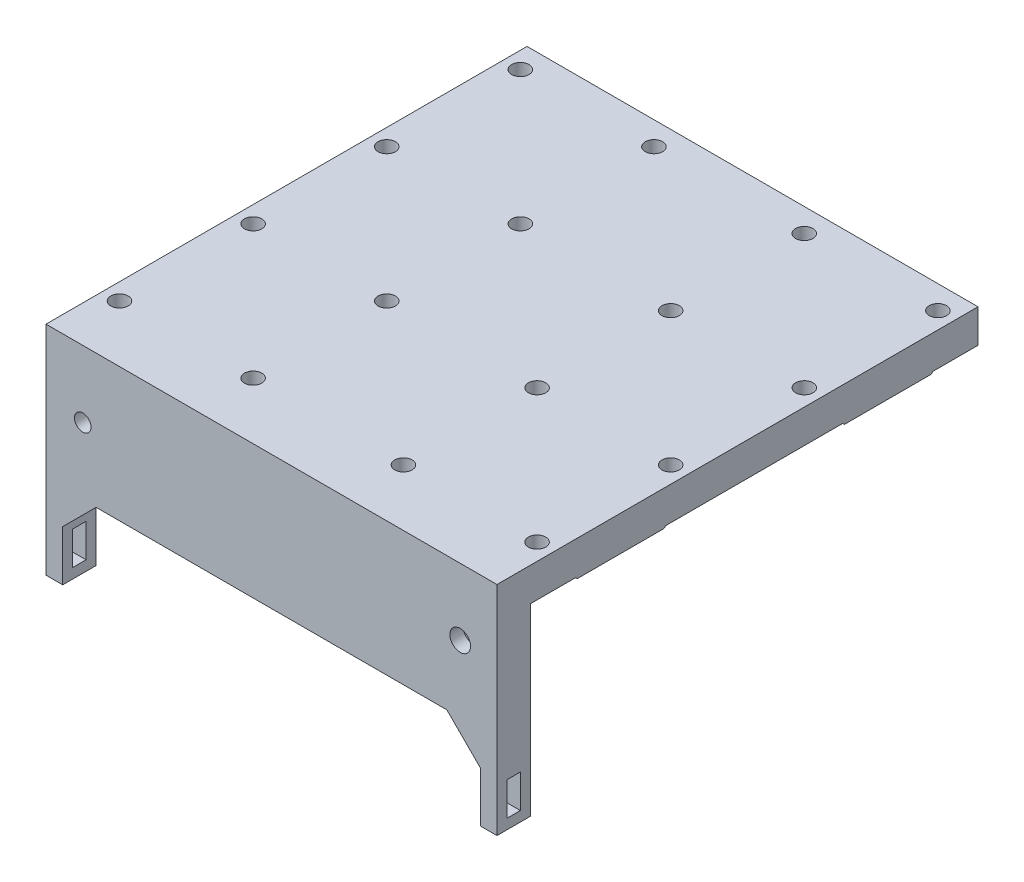
SolidWorks part; units mm, degrees
ref_plane "Płaszczyzna przednia" through (0, 0, 0) normal (0, 0, 1) x (1, 0, 0)
ref_plane "Płaszczyzna górna" through (0, 0, 0) normal (0, 1, 0) x (1, 0, 0)
ref_plane "Płaszczyzna prawa" through (0, 0, 0) normal (1, 0, 0) x (0, 0, -1)
sketch "Sketch1" plane through (0, 0, 0) normal (0, 1, 0) x (1, 0, 0)
  line L6 (-67.5, -67) -> (67.5, -67)
  line L12 (-67.5, -67) -> (-67.5, 67)
  line L18 (-67.5, 67) -> (67.5, 67)
  line L20 (67.5, -67) -> (67.5, 67)
  line L25 (-67.5, -67) -> (67.5, 67) construction
  line L26 (-67.5, 67) -> (67.5, -67) construction
  point P0 (0, 0)
  dimension "D1" = 134
  dimension "D2" = 135
extrude "Boss-Extrude1" add sketch "Sketch1" along normal blind 10
sketch "Sketch2" plane through (0, 0, 0) normal (0, 1, 0) x (1, 0, 0)
  line L0 (-67.5, 67) -> (-67.5, -67) construction
  line L1 (-67.5, 26.5) -> (-17.5, 26.5)
  line L2 (-67.5, 26.5) -> (-67.5, 53.5)
  line L3 (-67.5, 53.5) -> (-17.5, 53.5)
  line L4 (-17.5, 26.5) -> (-17.5, 53.5)
  line L5 (67.5, 67) -> (-67.5, 67) construction
  line L6 (-22, 0) -> (22, 0) construction
  line L7 (-17.5, -26.5) -> (-17.5, -53.5)
  line L8 (-67.5, -53.5) -> (-17.5, -53.5)
  line L9 (-67.5, -26.5) -> (-67.5, -53.5)
  line L10 (-67.5, -26.5) -> (-17.5, -26.5)
  line L11 (0, -22) -> (0, 22) construction
  line L12 (67.5, -26.5) -> (17.5, -26.5)
  line L13 (67.5, -26.5) -> (67.5, -53.5)
  line L14 (67.5, -53.5) -> (17.5, -53.5)
  line L15 (17.5, -26.5) -> (17.5, -53.5)
  line L16 (17.5, 26.5) -> (17.5, 53.5)
  line L17 (67.5, 53.5) -> (17.5, 53.5)
  line L18 (67.5, 26.5) -> (67.5, 53.5)
  line L19 (67.5, 26.5) -> (17.5, 26.5)
  dimension "D1" = 50
  dimension "D2" = 27
  dimension "D3" = 13.5
extrude "Boss-Extrude2" add sketch "Sketch2" against normal blind 0.5
sketch "Sketch3" plane through (0, 0, 0) normal (0, 1, 0) x (1, 0, 0)
  line L0 (-67.5, 67) -> (-67.5, -67) construction
  line L1 (-62.5, 20) -> (-22.5, 20) construction
  line L2 (-62.5, 20) -> (-62.5, 60) construction
  line L3 (-62.5, 60) -> (-22.5, 60) construction
  line L4 (-22.5, 20) -> (-22.5, 60) construction
  line L5 (67.5, 67) -> (-67.5, 67) construction
  line L6 (-22, 0) -> (22, 0) construction
  line L7 (-22.5, -20) -> (-22.5, -60) construction
  line L8 (-62.5, -60) -> (-22.5, -60) construction
  line L9 (-62.5, -20) -> (-62.5, -60) construction
  line L10 (-62.5, -20) -> (-22.5, -20) construction
  line L11 (0, -22) -> (0, 22) construction
  line L12 (62.5, -20) -> (22.5, -20) construction
  line L13 (62.5, -20) -> (62.5, -60) construction
  line L14 (62.5, -60) -> (22.5, -60) construction
  line L15 (22.5, -20) -> (22.5, -60) construction
  line L16 (22.5, 20) -> (22.5, 60) construction
  line L17 (62.5, 60) -> (22.5, 60) construction
  line L18 (62.5, 20) -> (62.5, 60) construction
  line L19 (62.5, 20) -> (22.5, 20) construction
  circle A0 centre (-62.5, 20) radius 2.6
  circle A1 centre (-22.5, 20) radius 2.6
  circle A2 centre (-22.5, 60) radius 2.6
  circle A3 centre (-62.5, 60) radius 2.6
  circle A4 centre (-62.5, -60) radius 2.6
  circle A5 centre (-22.5, -60) radius 2.6
  circle A6 centre (-22.5, -20) radius 2.6
  circle A7 centre (-62.5, -20) radius 2.6
  circle A8 centre (62.5, -20) radius 2.6
  circle A9 centre (22.5, -20) radius 2.6
  circle A10 centre (22.5, -60) radius 2.6
  circle A11 centre (62.5, -60) radius 2.6
  circle A12 centre (62.5, 60) radius 2.6
  circle A13 centre (22.5, 60) radius 2.6
  circle A14 centre (22.5, 20) radius 2.6
  circle A15 centre (62.5, 20) radius 2.6
  dimension "D1" = 5.2
  dimension "D2" = 40
  dimension "D3" = 5
  dimension "D4" = 7
extrude "Cut-Extrude1" cut sketch "Sketch3" against normal through all both and the other way through all
sketch "Sketch4" plane through (0, 0, 0) normal (0, 0, 1) x (1, 0, 0)
  line L0 (67.5, 10) -> (67.5, 0) construction
  line L1 (-67.5, 10) -> (67.5, 10)
  line L2 (-67.5, 10) -> (-67.5, -30)
  line L3 (-67.5, -30) -> (67.5, -30)
  line L4 (67.5, 10) -> (67.5, -30)
  line L5 (-67.5, 0) -> (67.5, 0) construction
  dimension "D1" = 30
extrude "Boss-Extrude3" add sketch "Sketch4" along normal blind 10 from surface starting at face at (0, 5, 67)
sketch "Sketch5" plane through (0, 0, 0) normal (0, 0, 1) x (1, 0, 0)
  line L0 (-67.5, -10) -> (67.5, -10) construction
  line L1 (-67.5, 10) -> (-67.5, -30) construction
  line L2 (67.5, -30) -> (67.5, 10) construction
  circle A0 centre (-56.5, -10) radius 2.4889
  circle A1 centre (56.5, -10) radius 3.1003
  dimension "D1" = 56.5
  dimension "D2" = 56.5
extrude "Cut-Extrude2" cut sketch "Sketch5" against normal through all both and the other way through all from surface starting at face at (0, -10, 77)
chamfer "Chamfer1" distance 0.5 angle 45 8 edges at (42.5, -0.5, 26.5) (42.5, -0.5, 53.5) (-42.5, -0.5, 53.5) (-42.5, -0.5, 26.5) (-42.5, -0.5, -53.5) (-42.5, -0.5, -26.5) (42.5, -0.5, -26.5) (42.5, -0.5, -53.5)
sketch "Sketch6" plane through (0, 0, 0) normal (0, 0, 1) x (1, 0, 0)
  circle A0 centre (56.5, -10) radius 5.25
  circle A1 centre (-56.5, -10) radius 5.25
  dimension "D1" = 10.5
extrude "Cut-Extrude3" cut sketch "Sketch6" along normal blind 6 from surface starting at face at (-54.0111, -10, 67)
sketch "Sketch7" plane through (0, 0, 0) normal (1, 0, 0) x (0, 0, -1)
  line L0 (-67, -30) -> (-77, -30)
  line L1 (-67, -30) -> (-67, -55.0974)
  line L2 (-77, -30) -> (-77, -55.0974)
  line L3 (-67, -55.0974) -> (-77, -55.0974)
  line L5 (-70, -52.0974) -> (-74, -52.0974)
  line L6 (-70, -52.0974) -> (-70, -42.0974)
  line L7 (-70, -42.0974) -> (-74, -42.0974)
  line L8 (-74, -52.0974) -> (-74, -42.0974)
  dimension "D1" = 3
  dimension "D2" = 3
  dimension "D3" = 10
  dimension "D4" = 3
  dimension "D5" = 25.0974
extrude "Boss-Extrude4" add sketch "Sketch7" along normal blind 5 from surface starting at face at (-67.5, -3, 11)
extrude "Boss-Extrude5" add sketch "Sketch7<2>" against normal blind 5 from surface starting at face at (67.5, -3, 11)
sketch "Sketch7<2>" plane through (0, 0, 0) normal (1, 0, 0) x (0, 0, -1) same geometry as "Sketch7"
chamfer "Chamfer2" distance 10 angle 45 2 edges at (-62.5, -30, 72) (62.5, -30, 72)
